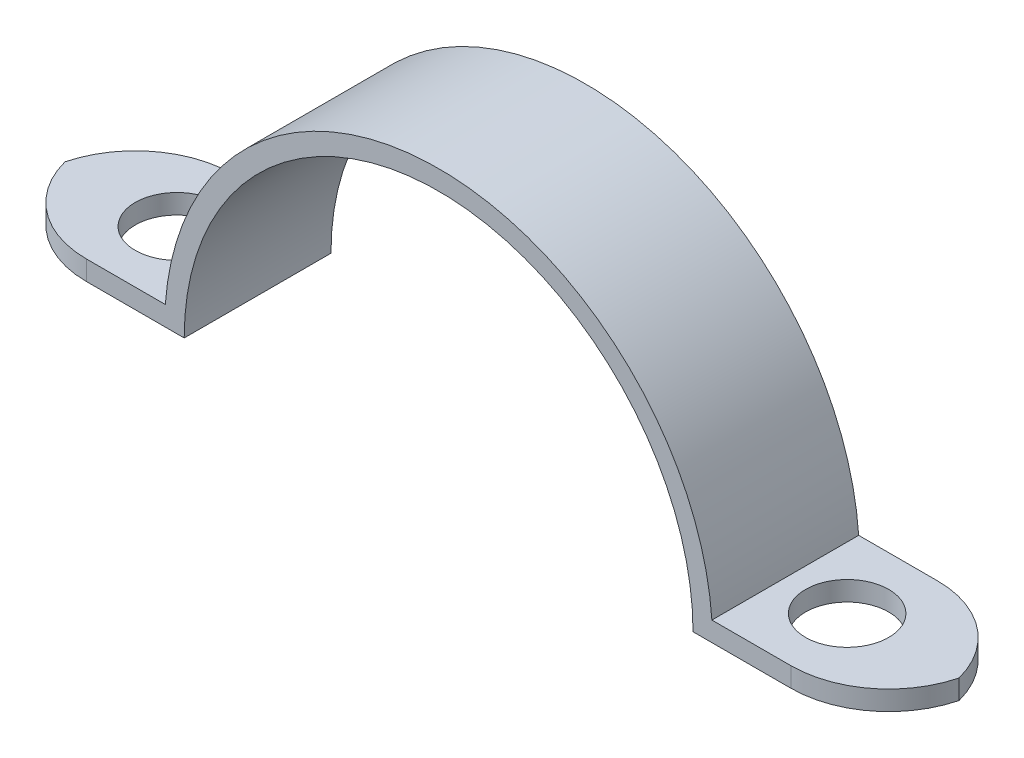
SolidWorks part; units mm, degrees
ref_plane "Front Plane" through (0, 0, 0) normal (0, 0, 1) x (1, 0, 0)
ref_plane "Top Plane" through (0, 0, 0) normal (0, 1, 0) x (1, 0, 0)
ref_plane "Right Plane" through (0, 0, 0) normal (1, 0, 0) x (0, 0, -1)
sketch "Sketch1" plane through (0, 0, 0) normal (0, 0, 1) x (1, 0, 0)
  line L0 (-37.8084, 0) -> (30.1006, 0) construction
  line L1 (-26, 0) -> (-46, 0)
  line L2 (26, 0) -> (46, 0)
  arc A1 (26, 0) -> (-26, 0) centre (0, 0) ccw
  dimension "D1" = 52
  dimension "D2" = 20
  dimension "D3" = 20
extrude "Extrude-Thin2" add sketch "Sketch1" against normal blind 15 thin thin type one direction reverse wall 2
sketch "Sketch6" plane through (0, 2, 0) normal (0, 1, 0) x (1, 0, 0)
  line L0 (-46, 15) -> (-46, 0) construction
  line L1 (-46, 15) -> (-27.9285, 15) construction
  circle A0 centre (-34.25, 7.5) radius 4.25
  circle A1 centre (34.25, 7.5) radius 4.25
  dimension "D1" = 8.5
  dimension "D2" = 68.5
  dimension "D3" = 11.75
  dimension "D4" = 7.5
extrude "Cut-Extrude1" cut sketch "Sketch6" against normal through all
fillet "Fillet1" radius 10 4 edges at (-46, 1, -15) (-46, 1, 0) (46, 1, -15) (46, 1, 0)
